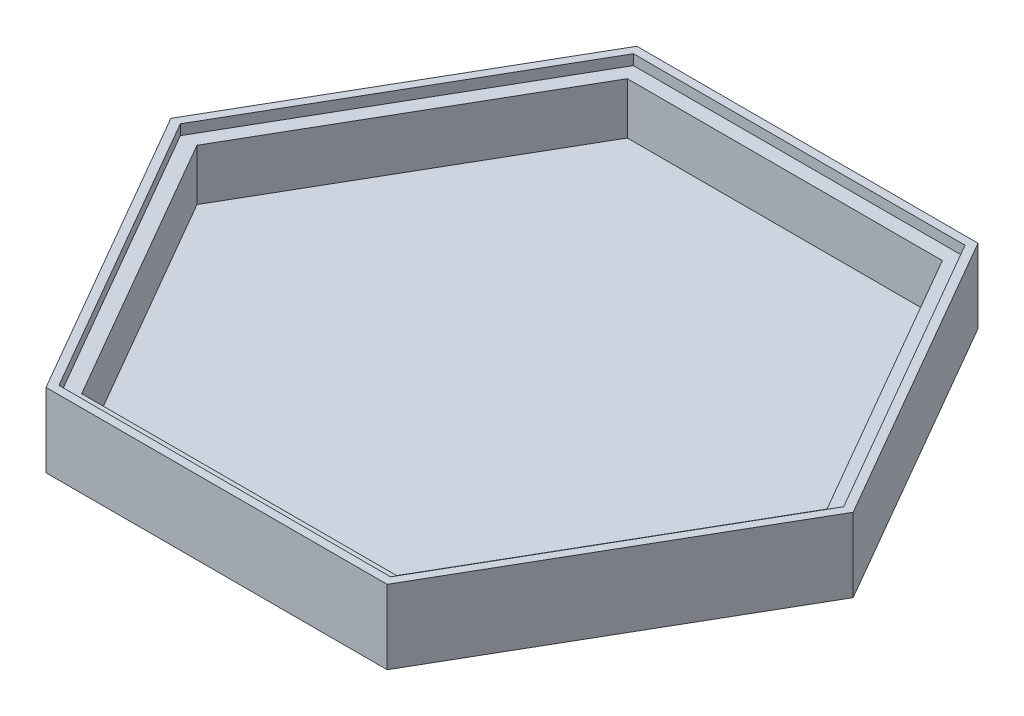
SolidWorks part; units mm, degrees
note: The reader was unsure of these and kept them because the rebuilt part matched: shared geometry of "Sketch1<3>", "Sketch1<4>".
ref_plane "Front Plane" through (0, 0, 0) normal (0, 0, 1) x (1, 0, 0)
ref_plane "Top Plane" through (0, 0, 0) normal (0, 1, 0) x (1, 0, 0)
ref_plane "Right Plane" through (0, 0, 0) normal (1, 0, 0) x (0, 0, -1)
sketch "Sketch1" plane through (0, 0, 0) normal (0, 1, 0) x (1, 0, 0)
  line L0 (32.2739, 55.9) -> (-32.2739, 55.9)
  line L1 (66.3953, 0) -> (33.1976, 57.5)
  line L2 (33.1976, 57.5) -> (-33.1976, 57.5)
  line L3 (-33.1976, 57.5) -> (-66.3953, 0)
  line L4 (-66.3953, 0) -> (-33.1976, -57.5)
  line L5 (-33.1976, -57.5) -> (33.1976, -57.5)
  line L6 (33.1976, -57.5) -> (66.3953, 0)
  line L7 (-32.2739, 55.9) -> (-64.5478, 0)
  line L8 (-64.5478, 0) -> (-32.2739, -55.9)
  line L9 (-32.2739, -55.9) -> (32.2739, -55.9)
  line L10 (32.2739, -55.9) -> (64.5478, 0)
  line L11 (64.5478, 0) -> (32.2739, 55.9)
  line L12 (-30.6573, 53.1) -> (-61.3146, 0)
  line L13 (-61.3146, 0) -> (-30.6573, -53.1)
  line L14 (-30.6573, -53.1) -> (30.6573, -53.1)
  line L15 (30.6573, -53.1) -> (61.3146, 0)
  line L16 (61.3146, 0) -> (30.6573, 53.1)
  line L17 (30.6573, 53.1) -> (-30.6573, 53.1)
  circle A0 centre (0, 0) radius 57.5 construction
  point P1 (0, 0)
  point P10 (4.2591, 5.0935)
  point P11 (0, 0)
  dimension "D1" = 115
  dimension "D2" = 1.6
  dimension "D3" = 2.8
extrude "Boss-Extrude1" add sketch "Sketch1" against normal blind 2.4 contours L5 L6 L1 L2 L3 L4 L11 L10 L9 L8 L7 L0 | L10 L11 L0 L7 L8 L9 L17 L16 L15 L14 L13 L12
extrude "Boss-Extrude2" add sketch "Sketch1<3>" along normal blind 10 contours L10 L11 L0 L7 L8 L9 L17 L16 L15 L14 L13 L12
sketch "Sketch1<3>" plane through (0, 0, 0) normal (0, 1, 0) x (1, 0, 0) same geometry as "Sketch1"
extrude "Boss-Extrude3" add sketch "Sketch1<4>" along normal blind 12 contours L5 L6 L1 L2 L3 L4 L11 L10 L9 L8 L7 L0
sketch "Sketch1<4>" plane through (0, 0, 0) normal (0, 1, 0) x (1, 0, 0) same geometry as "Sketch1"
